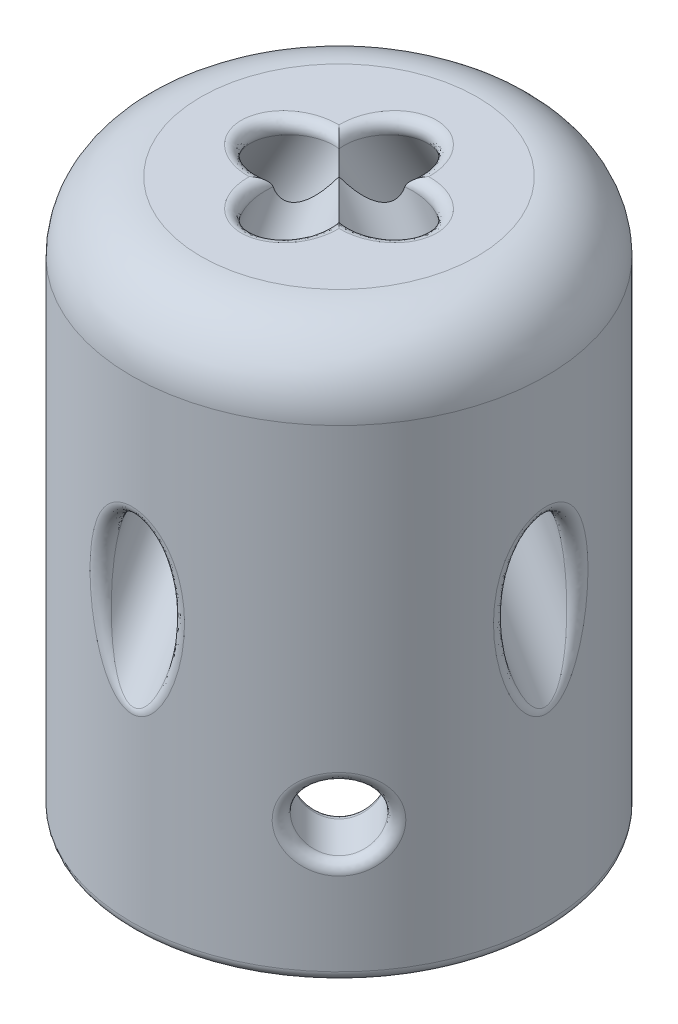
SolidWorks part; units mm, degrees
ref_plane "前视基准面" through (0, 0, 0) normal (0, 0, 1) x (1, 0, 0)
ref_plane "上视基准面" through (0, 0, 0) normal (0, 1, 0) x (1, 0, 0)
ref_plane "右视基准面" through (0, 0, 0) normal (1, 0, 0) x (0, 0, -1)
sketch "草图1" plane through (0, 0, 0) normal (0, 1, 0) x (1, 0, 0)
  circle A0 centre (0, 0) radius 6
  dimension "D1" = 12
extrude "凸台-拉伸1" add sketch "草图1" along normal blind 16
sketch "草图2" plane through (0, 0, 0) normal (0, -1, 0) x (1, 0, 0)
  circle A0 centre (0, 0) radius 4.1
  dimension "D1" = 8.2
extrude "切除-拉伸1" cut sketch "草图2" against normal blind 9.1
sketch "草图4" plane through (0, 16, 0) normal (0, 1, 0) x (1, 0, 0)
  line L0 (-1000, 0) -> (49000, 0) construction
  line L1 (0, -1000) -> (0, 49000) construction
ref_plane "基准面1" through (6.9282, 12, 0) normal (0.5, 0.866, 0) x (0, 0, -1)
sketch "草图5" plane through (6.9282, 12, 0) normal (0.5, 0.866, 0) x (0, 0, -1)
  line L0 (0, 174079.1062) -> (0, -215632.3255) construction
  line L1 (-201000, 8) -> (249000, 8) construction
  circle A0 centre (0, 9) radius 1
  dimension "D1" = 2
  dimension "D2" = 1
extrude "切除-拉伸2" cut sketch "草图5" against normal through all
sketch "草图6" plane through (0, 0, 0) normal (1, 0, 0) x (0, 0, -1)
  line L0 (0, -1000) -> (0, 49000) construction
pattern_circular "阵列(圆周)3" count 4 over 360 about axis through (0, -1000, 0) along (0, 1, 0) of "切除-拉伸2"
sketch "草图7" plane through (0, 16, 0) normal (0, 1, 0) x (1, 0, 0)
  line L0 (0, 0) -> (35355.3391, 35355.3391) construction
ref_plane "基准面2" through (0, 0, 0) normal (0.7071, 0, 0.7071) x (0.7071, 0, -0.7071)
sketch "草图8" plane through (0, 0, 0) normal (0.7071, 0, 0.7071) x (0.7071, 0, -0.7071)
  line L0 (-6, 0) -> (6, 0) construction
  circle A0 centre (0, 4) radius 1
  dimension "D1" = 2
  dimension "D2" = 4
extrude "切除-拉伸3" cut sketch "草图8" against normal through all and the other way through all
fillet "圆角1" radius 2 1 edges at (0, 16, 6)
fillet "圆角2" radius 0.3 4 edges at (-2.3094, 16, 0) (0, 16, -2.3094) (2.3094, 16, 0) (0, 16, 2.3094)
fillet "圆角3" radius 0.3 9 edges at (0, 0, 6) (-6, 5.6079, -0.0146) (0.0146, 5.6079, -6) (5.9978, 9.5847, -0.1634) (-0.0146, 5.6079, 6) (-4.8767, 3.7855, -3.4954) (3.4954, 4.2145, 4.8767) (-3.5082, 4.1974, -2.1219) (2.1219, 3.8026, 3.5082)
